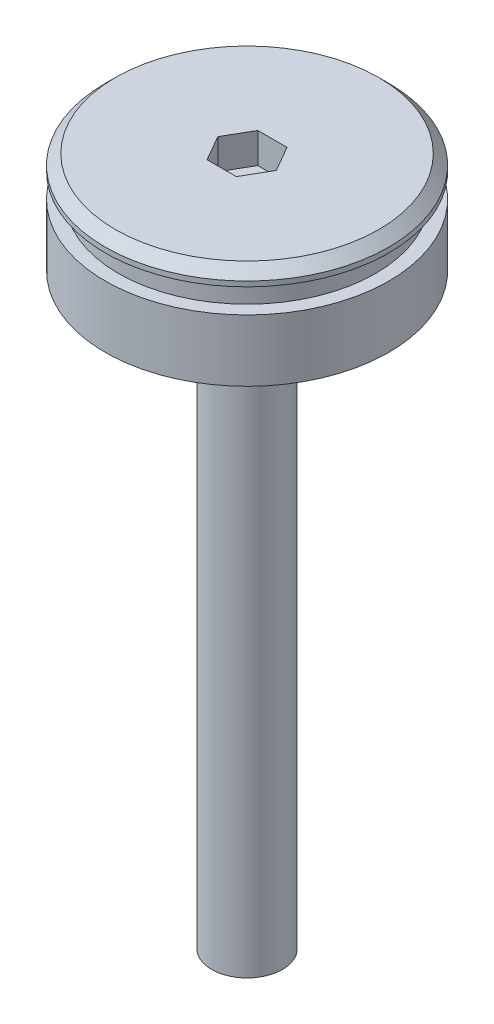
SolidWorks part; units mm, degrees
material "6061-T6 (SS)"
ref_plane "Piano frontale" through (0, 0, 0) normal (0, 0, 1) x (1, 0, 0)
ref_plane "Piano superiore" through (0, 0, 0) normal (0, 1, 0) x (1, 0, 0)
ref_plane "Piano destro" through (0, 0, 0) normal (1, 0, 0) x (0, 0, -1)
sketch "Schizzo1" plane through (0, 0, 0) normal (0, 0, 1) x (1, 0, 0)
  line L0 (0, 0) -> (0, 68)
  line L1 (0, 0) -> (-3.5, 0)
  line L2 (-3.5, 0) -> (-3.5, 58)
  line L3 (-3.5, 58) -> (-14, 58)
  line L4 (-14, 58) -> (-14, 68)
  line L5 (-14, 68) -> (0, 68)
  line L6 (0, 0) -> (0, 44.4338) construction
  line L10 (-14, 66.5) -> (-12.7, 66.5)
  line L11 (-12.7, 66.5) -> (-12.7, 64.1)
  line L12 (-12.7, 64.1) -> (-14, 64.1)
  dimension "D1" = 7
  dimension "D2" = 28
  dimension "D3" = 10
  dimension "D4" = 58
  dimension "D5" = 2.4
  dimension "D6" = 1.3
  dimension "D10" = 1.5
revolve "Rivoluzione1" add sketch "Schizzo1" angle 360 about L6 region at (-1.75, 0.6943, 0)
cosmetic thread "Filettatura cosmetica1" parameters "D1"=6, "D2"=4.891
chamfer "Smusso1" distance 1 angle 45 1 edges at (0, 68, -14)
sketch "Schizzo2" plane through (0, 68, 0) normal (0, 1, 0) x (1, 0, 0)
  line L6 (-2.8868, 0) -> (-1.4434, 2.5)
  line L7 (-1.4434, 2.5) -> (1.4434, 2.5)
  line L8 (1.4434, 2.5) -> (2.8868, 0)
  line L9 (2.8868, 0) -> (1.4434, -2.5)
  line L10 (1.4434, -2.5) -> (-1.4434, -2.5)
  line L11 (-1.4434, -2.5) -> (-2.8868, 0)
  circle A0 centre (0, 0) radius 2.8868
  dimension "D1" = 5
extrude "Taglio-Estrusione1" cut sketch "Schizzo2" against normal blind 3 contours L11 L10 L9 L8 L7 L6 region at (0, 68, 0)
